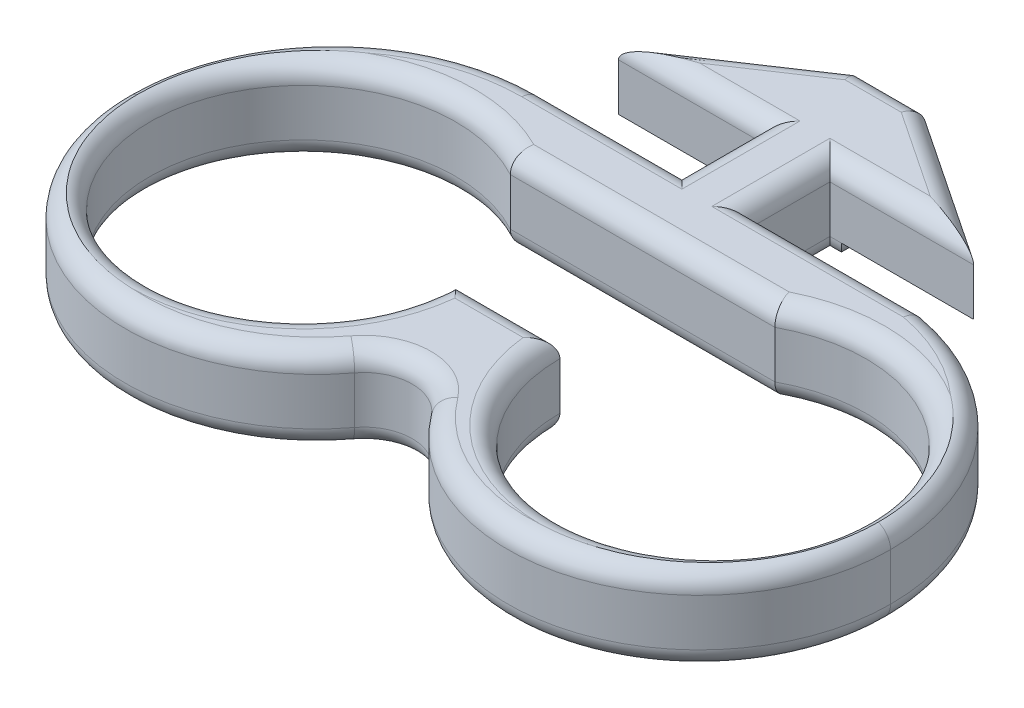
SolidWorks part; units mm, degrees
ref_plane "Front" through (0, 0, 0) normal (0, 0, 1) x (1, 0, 0)
ref_plane "Top" through (0, 0, 0) normal (0, 1, 0) x (1, 0, 0)
ref_plane "Right" through (0, 0, 0) normal (1, 0, 0) x (0, 0, -1)
sketch "Sketch1" plane through (0, 0, 0) normal (0, 1, 0) x (1, 0, 0)
  line L0 (-1.7907, 2.125) -> (-9.398, 2.125)
  line L2 (-1.7907, -2.125) -> (-1.7907, 2.125)
  line L4 (1.7907, -2.125) -> (1.7907, 2.125)
  line L7 (-9.398, 2.125) -> (-1.7907, 7.205)
  line L8 (-1.7907, 7.205) -> (1.7907, 7.205)
  line L9 (1.7907, 7.205) -> (9.398, 2.125)
  line L10 (9.398, 2.125) -> (1.7907, 2.125)
  line L11 (1.7907, -2.125) -> (20.25, -2.125)
  line L12 (-1.7907, -2.125) -> (-20.25, -2.125)
  line L13 (-20.25, -2.125) -> (-20.25, -13.1232)
  line L14 (-20.25, -13.1232) -> (20.25, -13.1232)
  line L15 (20.25, -13.1232) -> (20.25, -2.125)
  line L16 (20.25, -2.125) -> (1.7907, -2.125)
  point P0 (0, 0)
  point P17 (0, 7.205)
  point P19 (0, -13.1232)
  point P24 (1.7907, 0)
  dimension "D1" = 18.796
  dimension "D2" = 3.5814
  dimension "D3" = 40.5
  dimension "D4" = 10.9982
  dimension "D5" = 5.08
  dimension "4.2" = 4.25
extrude "Boss-Extrude1" add sketch "Sketch1" along normal blind 4.5 contours L14 L15 L11 L4 L10 L9 L8 L7 L0 L2 L12 L13 region at (0, 0, 6.1133)
sketch "Sketch3" plane through (0, 4.5, 0) normal (0, 1, 0) x (1, 0, 0)
  line L3 (-20.25, -13.1232) -> (20.25, -13.1232) construction
  line L16 (-20.25, -13.1232) -> (20.25, -13.1232)
  line L17 (20.25, -13.1232) -> (20.25, -2.125)
  line L18 (20.25, -2.125) -> (1.7907, -2.125)
  line L19 (1.7907, -2.125) -> (1.7907, 2.125)
  line L20 (1.7907, 2.125) -> (9.398, 2.125)
  line L21 (9.398, 2.125) -> (1.7907, 7.205)
  line L22 (1.7907, 7.205) -> (-1.7907, 7.205)
  line L23 (-1.7907, 7.205) -> (-9.398, 2.125)
  line L24 (-9.398, 2.125) -> (-1.7907, 2.125)
  line L25 (-1.7907, 2.125) -> (-1.7907, -2.125)
  line L26 (-1.7907, -2.125) -> (-20.25, -2.125)
  line L27 (-20.25, -2.125) -> (-20.25, -13.1232)
  line L28 (-20.25, -13.1232) -> (20.25, -13.1232)
  arc A2 (-20.25, -13.1232) -> (-2.0306, -19.2057) centre (-10.125, -13.1232) ccw
  arc A3 (2.0306, -19.2057) -> (20.25, -13.1232) centre (10.125, -13.1232) ccw
  arc A4 (2.0306, -19.2057) -> (-2.0306, -19.2057) centre (0, -20.7315) ccw
  point P14 (0, -13.1232)
  line M15 (-20.25, -13.1232) -> (20.25, -13.1232)
  dimension "D2" = 2.54
  dimension "D1" = 0
extrude "Boss-Extrude2" add sketch "Sketch3" against normal up to surface (4.5 mm away) contours A2 M15 | L28 A3 region at (0, 4.5, 17.4155) up to face at (0, 0, 0.9864)
sketch "Sketch4" plane through (0, 4.5, 0) normal (0, 1, 0) x (1, 0, 0)
  line L1 (2.75, -13.1232) -> (-2.75, -13.1232) construction
  circle A0 centre (-10.85, -13.1232) radius 8.1
  circle A1 centre (10.85, -13.1232) radius 8.1
  point P4 (0, -13.1232)
  dimension "D1" = 16.2
  dimension "D2" = 21.7
extrude "Cut-Extrude2" cut sketch "Sketch4" against normal through all
sketch "Sketch5" plane through (0, 4.5, 0) normal (0, 1, 0) x (1, 0, 0)
  line L2 (7, -5.9967) -> (-7, -5.9967)
  line L10 (-2.75, -13.1232) -> (2.75, -13.1232)
  circle A0 centre (-10.85, -13.1232) radius 8.1 construction
  circle A1 centre (10.85, -13.1232) radius 8.1 construction
  arc A8 (7, -5.9967) -> (2.75, -13.1232) centre (10.85, -13.1232) ccw
  arc A9 (-2.75, -13.1232) -> (-7, -5.9967) centre (-10.85, -13.1232) ccw
  point P12 (0, -15.6632)
  point P28 (0, -10.5832)
  dimension "D2" = 14
  dimension "D3" = 2.54
  dimension "D10" = 2.54
extrude "Cut-Extrude4" cut sketch "Sketch5" against normal up to next contours A9 L2 A8 L10
sketch "Sketch6" plane through (0, 4.5, 0) normal (0, 1, 0) x (1, 0, 0)
  line L0 (-9.2518, -2.125) -> (-20.25, -2.125)
  line L1 (-20.25, -2.125) -> (-20.25, -13.1232)
  line L2 (-1.7907, -2.125) -> (-20.25, -2.125) construction
  line L3 (20.25, -13.1232) -> (20.25, -2.125)
  line L4 (20.25, -2.125) -> (11.0204, -2.125)
  line L5 (1.7907, -2.125) -> (20.25, -2.125) construction
  arc A0 (-9.2518, -2.125) -> (-20.25, -13.1232) centre (-9.2518, -13.1232) ccw
  arc A2 (20.25, -13.1232) -> (11.0204, -2.125) centre (9.0824, -13.1232) ccw
extrude "Cut-Extrude5" cut sketch "Sketch6" against normal up to next
sketch "Sketch8" plane through (0, 0, 0) normal (0, -1, 0) x (1, 0, 0)
  line L0 (1.7907, 2.125) -> (11.0204, 2.125) construction
  line L1 (-9.398, -2.125) -> (-2.398, -2.125)
  line L2 (-9.398, -2.125) -> (-9.398, -3.125)
  line L3 (-9.398, -3.125) -> (-2.398, -3.125)
  line L4 (-2.398, -2.125) -> (-2.398, -3.125)
  line L5 (9.398, -2.125) -> (2.398, -2.125)
  line L6 (9.398, -2.125) -> (9.398, -3.125)
  line L7 (9.398, -3.125) -> (2.398, -3.125)
  line L8 (2.398, -2.125) -> (2.398, -3.125)
  line L9 (-2.3, 2.125) -> (-9.398, 2.125)
  line L10 (-2.3, 2.125) -> (-2.3, 3.125)
  line L11 (-2.3, 3.125) -> (-9.398, 3.125)
  line L12 (-9.398, 2.125) -> (-9.398, 3.125)
  line L13 (2.398, 2.125) -> (9.398, 2.125)
  line L14 (2.398, 2.125) -> (2.398, 3.125)
  line L15 (2.398, 3.125) -> (9.398, 3.125)
  line L16 (9.398, 2.125) -> (9.398, 3.125)
extrude "Cut-Extrude9" cut sketch "Sketch8" against normal blind 1
fillet "Fillet1" radius 1 47 edges at (17.8068, 4.5, 17.272) (0, 4.5, 5.9967) (-17.8068, 4.5, 17.272) (0, 4.5, 13.1232) (-5.5212, 4.5, 2.125) (-1.7907, 4.5, 0) (-5.5943, 4.5, -2.125) (-5.5943, 4.5, -4.665) (0, 4.5, -7.205) (5.5943, 4.5, -4.665) (5.5943, 4.5, -2.125) (1.7907, 4.5, 0) (6.4055, 4.5, 2.125) (17.6369, 4.5, 5.9443) (13.3312, 4.5, 22.7271) (0, 4.5, 18.1915) (-13.3312, 4.5, 22.7271) (-17.0287, 4.5, 5.3463) (0, 0, -7.205) (-4.8456, 0, -5.165) (-5.1492, 0, -3.125) (-2.398, 0, -2.625) (-2.0943, 0, -2.125) (-1.7907, 0, 0) (-2.0453, 0, 2.125) (-2.3, 0, 2.625) (-5.849, 0, 3.125) (-9.398, 0, 2.6255) (-17.0802, 0, 5.3982) (-13.3312, 0, 22.7271) (0, 0, 18.1915) (13.3312, 0, 22.7271) (17.6369, 0, 5.9443) (10.2092, 0, 2.125) (9.398, 0, 2.625) (5.898, 0, 3.125) (2.398, 0, 2.625) (2.0943, 0, 2.125) (1.7907, 0, 0) (2.0943, 0, -2.125) (2.398, 0, -2.625) (5.1492, 0, -3.125) (4.8456, 0, -5.165) (0, 0, 5.9967) (17.8068, 0, 17.272) (0, 0, 13.1232) (-17.8068, 0, 17.272)
sketch "Sketch10" plane through (0, 0, 0) normal (0, -1, 0) x (-1, 0, 0)
  text T0 "3V" font "Helonia" height in points 10
extrude "Cut-Extrude10" cut sketch "Sketch10" against normal blind 1
